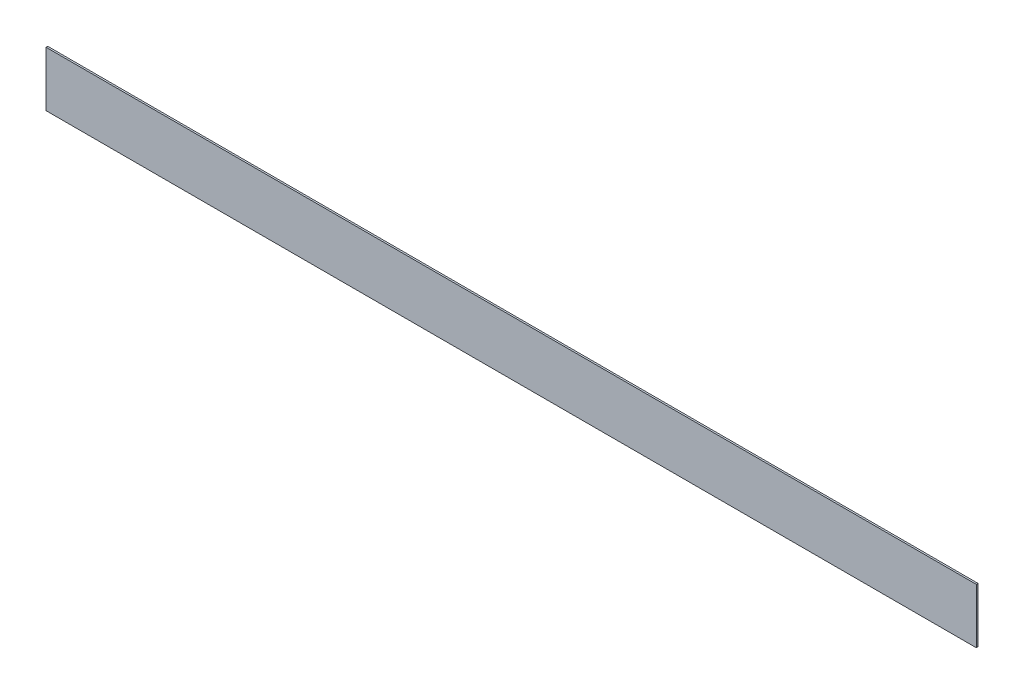
SolidWorks part; units mm, degrees
ref_plane "Front Plane" through (0, 0, 0) normal (0, 0, 1) x (1, 0, 0)
ref_plane "Top Plane" through (0, 0, 0) normal (0, 1, 0) x (1, 0, 0)
ref_plane "Right Plane" through (0, 0, 0) normal (1, 0, 0) x (0, 0, -1)
sketch "Sketch1" plane through (0, 0, 0) normal (1, 0, 0) x (0, 0, -1)
  line L1 (-9.7865, 33.7238) -> (-6.6115, 33.7238)
  line L2 (-9.7865, 33.7238) -> (-9.7865, -67.8762)
  line L3 (-9.7865, -67.8762) -> (-6.6115, -67.8762)
  line L4 (-6.6115, 33.7238) -> (-6.6115, -67.8762)
  dimension "D1" = 3.175
  dimension "D2" = 101.6
extrude "Boss-Extrude1" add sketch "Sketch1" along normal blind 1720.85
